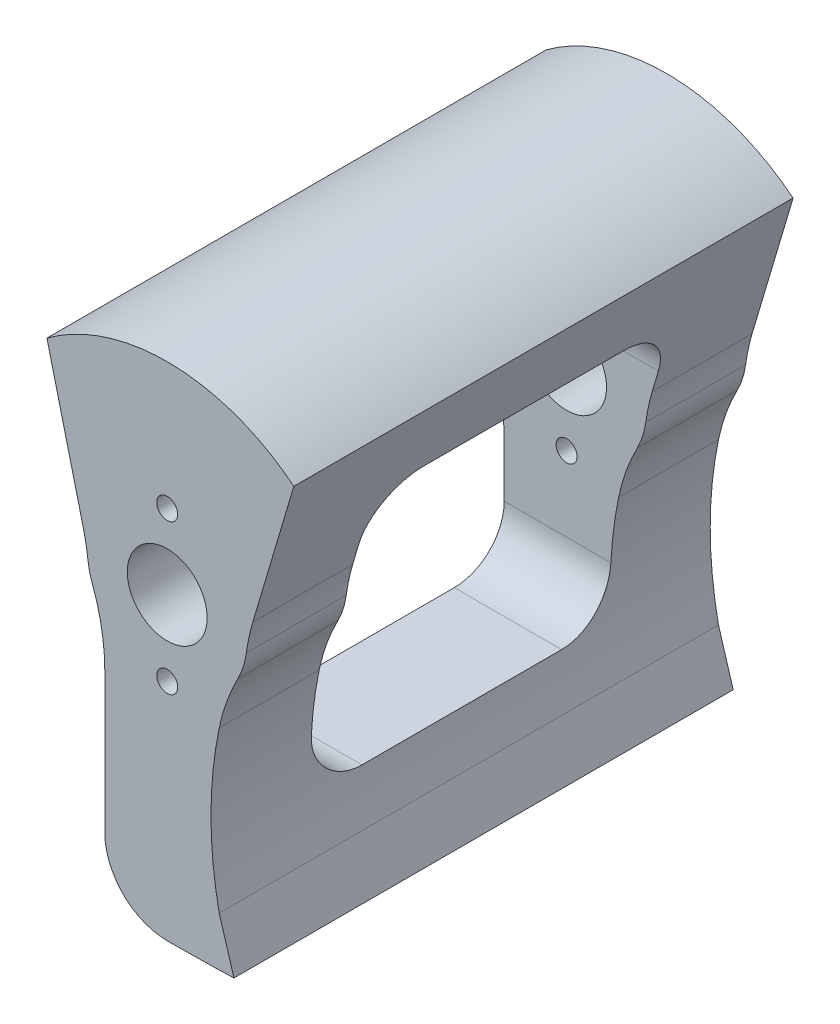
SolidWorks part; units mm, degrees
other "Markup1"
sketch "Sketch11" plane through (-24.0999, -60, 50) normal (0, 0, 1) x (1, 0, 0)
material "AISI 4340 Steel, annealed"
ref_plane "Front Plane" through (0, 0, 0) normal (0, 0, 1) x (1, 0, 0)
ref_plane "Top Plane" through (0, 0, 0) normal (0, 1, 0) x (1, 0, 0)
ref_plane "Right Plane" through (0, 0, 0) normal (1, 0, 0) x (0, 0, -1)
sketch "Sketch4" plane through (0, 0, 0) normal (0, 0, 1) x (1, 0, 0)
  line L0 (-16, 0) -> (16, 0)
  line L1 (-12.5, -60) -> (12.5, -60)
  line L2 (-12.5, -60) -> (-12.5, 60)
  line L3 (-12.5, 60) -> (12.5, 60)
  line L4 (12.5, -60) -> (12.5, 60)
  line L5 (-12.5, -60) -> (12.5, 60) construction
  line L6 (-12.5, 60) -> (12.5, -60) construction
  line L7 (12.5, -60) -> (10.4167, -50)
  line L8 (10.4167, -50) -> (13.3636, -59.7804)
  line L9 (0, 0) -> (0, -60)
  circle A0 centre (0, 0) radius 8
  circle A1 centre (0, 0) radius 16
  circle A2 centre (0, 0) radius 60
  arc A3 (10.4167, -50) -> (12.5, -9.9875) centre (87.4538, -33.9506) cw
  circle A4 centre (10.4167, -50) radius 10.2147 construction
  arc A5 (0, -60) -> (13.3636, -59.7804) centre (0, 346.6769) ccw
  point P12 (0, 0)
  dimension "D1" = 16
  dimension "D2" = 32
  dimension "D6" = 5
  dimension "D3" = 25
  dimension "D4" = 120
  dimension "D5" = 10
extrude "Boss-Extrude1" add sketch "Sketch4" along normal mid plane 100 contours L9 A1 L4 L0 A0 | L4 A1 L0 | L7 A3 A1 L9 A2 | L7 A2 L4 L8 | L4 A2 L8 | L4 A5 L8 A2 | A2 A5 L7 | L7 A5 L4 A2 | L0 A1 L2 | L2 A1 L9 A0 L0 | L2 A2 L9 A1 region at (6.7958, -8.6963, 0) region at (-6.7958, -8.6963, 0) region at (13.914, -3.8067, 0) region at (-13.914, -3.8067, 0) region at (5.0815, -37.5531, 0) region at (-6.3507, -36.8383, 0) region at (9.2691, -59.5639, 0) region at (12.6668, -58.0577, 0) region at (11.7711, -55.4389, 0) region at (12.4107, -59.1243, 0) region at (12.8543, -59.2604, 0)
fillet "Fillet1" radius 12.5 1 edges at (-12.5, -58.6835, 0)
fillet "Fillet2" radius 40 2 edges at (12.5, -9.9875, 0) (-12.5, -9.9875, 0)
ref_axis "Axis1" through (0, 0, -55) along (0, 0, 1)
sketch "Sketch7" plane through (0, 0, 0) normal (1, 0, 0) x (0, 0, -1)
  line L0 (55, 0) -> (-55, 0) construction
  line L1 (-30, -40) -> (30, -40)
  line L2 (-30, -40) -> (-30, 0)
  line L3 (-30, 0) -> (30, 0)
  line L4 (30, -40) -> (30, 0)
  line L5 (-30, -40) -> (30, 0) construction
  line L6 (-30, 0) -> (30, -40) construction
  line L7 (-50, 0) -> (-50, -7.4377) construction
  line L8 (50, -7.4377) -> (50, 0) construction
  line L9 (-50, -60) -> (50, -60) construction
  point P0 (0, -20)
  dimension "D1" = 20
  dimension "D2" = 20
  dimension "D3" = 20
extrude "Cut-Extrude1" cut sketch "Sketch7" against normal through all both and the other way through all
fillet "Fillet3" radius 10 2 edges at (-1.7523, -40, -30) (-1.7523, -40, 30)
sketch "Sketch8" plane through (0, 0, 0) normal (0, 0, 1) x (1, 0, 0)
  line L0 (-16, 0) -> (-16, 32.0006) construction
  line L1 (16, 0) -> (16, 37.1511)
  line L2 (0, 0) -> (0, 40.45) construction
  line L3 (-16, 0) -> (-24.0999, 32.4869)
  line L4 (-16, 0) -> (16, 0)
  line L5 (16, 0) -> (25.3636, 31.5101)
  circle A0 centre (0, 0) radius 8
  circle A1 centre (0, 0) radius 16
  circle A2 centre (0, 0) radius 40.45
  point P13 (0, 0)
  dimension "D1" = 16
  dimension "D2" = 32
  dimension "D3" = 14
  dimension "D4" = 40.45
  dimension "D5" = 16.55
extrude "Boss-Extrude2" add sketch "Sketch8" along normal mid plane 100 contours L4 A1 A0 | L1 A2 L3 A1 | L5 A2 L1 region at (-2.8198, 25.3852, 0) region at (19.1463, 23.0643, 0) region at (12, 0.3578, 0)
fillet "Fillet5" radius 40 4 edges at (-16, 0, 40) (-16, 0, -40) (16, 0, -40) (16, 0, 40)
sketch "Sketch9" plane through (0, 0, 0) normal (1, 0, 0) x (0, 0, -1)
  line L0 (55, 0) -> (-55, 0) construction
  line L1 (30, 18) -> (-30, 18)
  line L2 (30, 18) -> (30, 0)
  line L3 (30, 0) -> (-30, 0)
  line L4 (-30, 18) -> (-30, 0)
  line L5 (30, 18) -> (-30, 0) construction
  line L6 (30, 0) -> (-30, 18) construction
  line L9 (-50, -2.1509) -> (-50, -7.4377) construction
  line L10 (50, -7.4377) -> (50, -2.1509) construction
  point P0 (0, 9)
  dimension "D1" = 20
  dimension "D2" = 20
  dimension "D3" = 18
extrude "Cut-Extrude2" cut sketch "Sketch9" against normal through all both and the other way through all
fillet "Fillet4" radius 10 2 edges at (0.4305, 18, -30) (0.4305, 18, 30)
sketch "Sketch10" plane through (0, 0, 50) normal (0, 0, 1) x (1, 0, 0)
  circle A0 centre (0, 15) radius 2.1
  circle A1 centre (0, -15) radius 2.1
  dimension "D1" = 4.2
  dimension "4.2" = 4.2
  dimension "D2" = 15
  dimension "D3" = 15
extrude "Cut-Extrude3" cut sketch "Sketch10" against normal through all both and the other way through all
